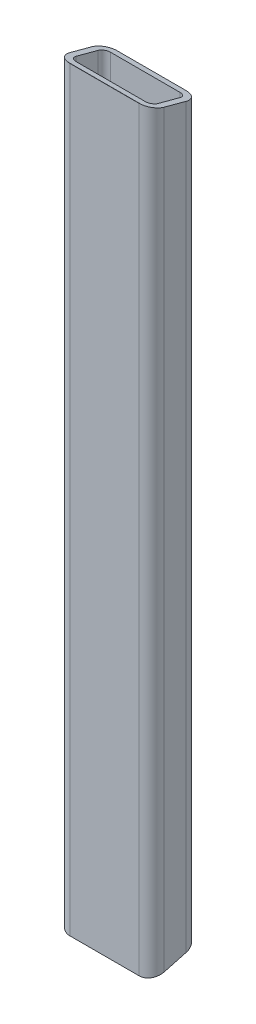
SolidWorks part; units mm, degrees
material "Ст 3 ГОСТ 380-88"
ref_plane "Спереди" through (0, 0, 0) normal (0, 0, 1) x (1, 0, 0)
ref_plane "Сверху" through (0, 0, 0) normal (0, 1, 0) x (1, 0, 0)
ref_plane "Справа" through (0, 0, 0) normal (1, 0, 0) x (0, 0, -1)
sketch "Эскиз1" plane through (0, 0, 0) normal (0, 1, 0) x (1, 0, 0)
  line L0 (-15, 7.5) -> (15, -7.5) construction
  line L1 (-11, 7.5) -> (11, 7.5)
  line L2 (-15, 3.5) -> (-15, -3.5)
  line L3 (-11, -7.5) -> (11, -7.5)
  line L4 (15, 3.5) -> (15, -3.5)
  line L5 (-15, -7.5) -> (15, 7.5) construction
  arc A0 (-15, -3.5) -> (-11, -7.5) centre (-11, -3.5) ccw
  arc A1 (11, -7.5) -> (15, -3.5) centre (11, -3.5) ccw
  arc A2 (11, 7.5) -> (15, 3.5) centre (11, 3.5) cw
  arc A3 (-11, 7.5) -> (-15, 3.5) centre (-11, 3.5) ccw
  point P4 (0, 0)
  dimension "D3" = 4
  dimension "D1" = 30
  dimension "D2" = 15
extrude "Вытянуть-Тонкостенный1" add sketch "Эскиз1" along normal blind 120 and the other way blind 120 thin
chamfer "Фаска1" distance 4 angle 75 2 edges at (0, 120, -7.5) (0, -120, -7.5)
